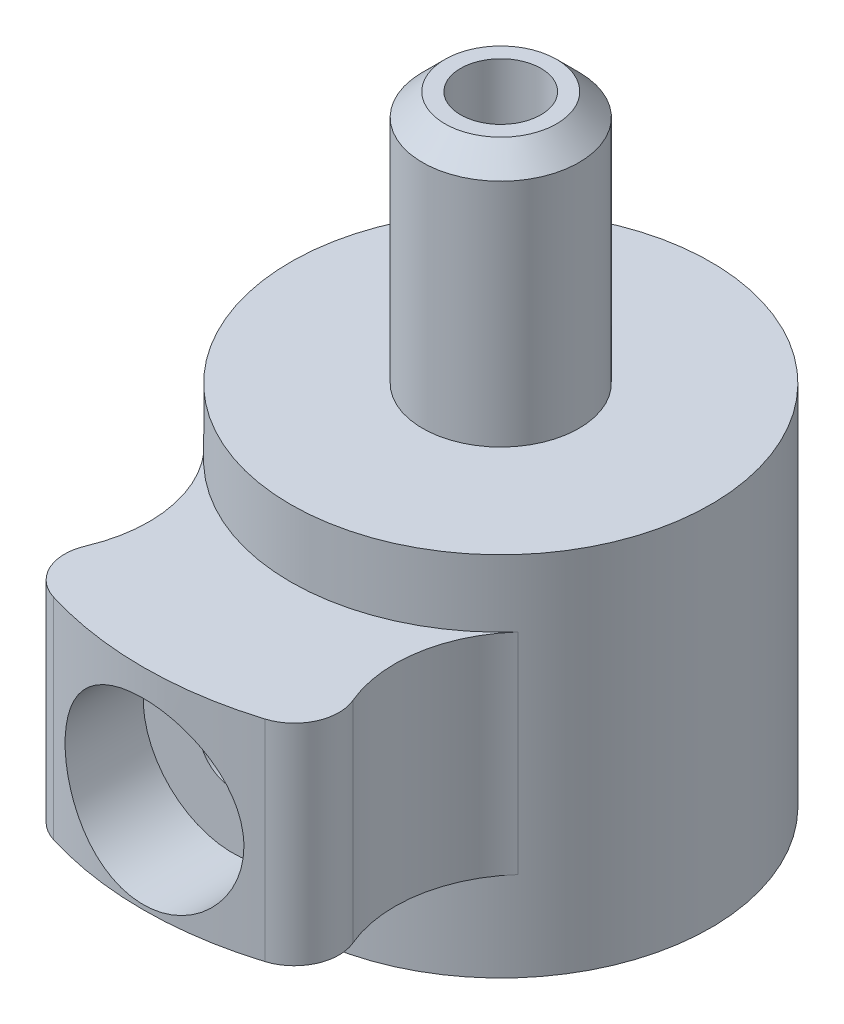
SolidWorks part; units mm, degrees
material "1060 Сплав"
ref_plane "Front Plane" through (0, 0, 0) normal (0, 0, 1) x (1, 0, 0)
ref_plane "Top Plane" through (0, 0, 0) normal (0, 1, 0) x (1, 0, 0)
ref_plane "Right Plane" through (0, 0, 0) normal (1, 0, 0) x (0, 0, -1)
sketch "Эскиз1" plane through (0, 0, 0) normal (1, 0, 0) x (0, 0, -1)
  line L0 (0, 0) -> (0, 10.689) construction
  line L1 (-3.4, 0) -> (-3.4, 6.5)
  line L2 (-3.4, 6.5) -> (-0.9, 6.5)
  line L3 (-0.9, 6.5) -> (-0.9, 13.85)
  line L4 (-0.9, 13.85) -> (-1.75, 13.85)
  line L5 (-1.75, 13.85) -> (-1.75, 8.2)
  line L6 (-1.75, 8.2) -> (-8, 8.2)
  line L7 (-8, 8.2) -> (-8, 0)
  line L8 (-8, 0) -> (-3.4, 0)
  line L9 (0, 0) -> (-3.4, 0) construction
  dimension "D1" = 6.8
  dimension "D2" = 1.8
  dimension "D3" = 3.5
  dimension "D4" = 16
  dimension "D5" = 8.2
  dimension "D6" = 13.85
  dimension "D7" = 6.5
revolve "Повернуть1" add sketch "Эскиз1" angle 360 about L0
sketch "Эскиз2" plane through (0, 8.2, 0) normal (0, 1, 0) x (1, 0, 0)
  line L0 (-5.75, -5.1213) -> (0, 0) construction
  line L1 (0, 0) -> (5.75, -5.1213) construction
  line L2 (-5.75, -5.1213) -> (5.75, -5.1213) construction
  line L3 (0, 0) -> (0, -5.1213) construction
  arc A0 (-5.75, -5.1213) -> (5.75, -5.1213) centre (0, 0) cw construction
  arc A1 (7.9903, -7.1166) -> (-7.9903, -7.1166) centre (0, 0) ccw
  arc A2 (3.5097, -3.126) -> (-3.5097, -3.126) centre (0, 0) ccw
  arc A3 (3.5097, -3.126) -> (7.9903, -7.1166) centre (5.75, -5.1213) ccw
  arc A4 (-7.9903, -7.1166) -> (-3.5097, -3.126) centre (-5.75, -5.1213) ccw
  point P4 (0, 7.7)
  dimension "D1" = 6
  dimension "D2" = 4.7
  dimension "D3" = 11.5
extrude "Вырез-Вытянуть1" cut sketch "Эскиз2" against normal through all
fillet "Скругление1" radius 1 2 edges at (3.5553, 4.1, 7.1666) (-3.5553, 4.1, 7.1666)
ref_plane "Плоскость1" through (0, 8.2, 8) normal (0, 0, 1) x (1, 0, 0)
sketch "Эскиз3" plane through (0, 8.2, 8) normal (0, 0, 1) x (1, 0, 0)
  line L0 (-2.3648, -4.1) -> (0, -4.1) construction
  line L1 (-2.3648, 0) -> (-2.3648, -8.2) construction
  line L2 (0, -4.1) -> (0, 0) construction
  line L3 (2.3648, 0) -> (-2.3648, 0) construction
  circle A0 centre (0, -4.1) radius 0.75
  dimension "D1" = 1.5
extrude "Вырез-Вытянуть2" cut sketch "Эскиз3" against normal up to next
sketch "Эскиз4" plane through (0, 8.2, 8) normal (0, 0, 1) x (1, 0, 0)
  circle A0 centre (0, -4.1) radius 2
  dimension "D1" = 4
extrude "Вырез-Вытянуть3" cut sketch "Эскиз4" against normal blind 2
sketch "Эскиз5" plane through (0, 8.2, 0) normal (0, 1, 0) x (1, 0, 0)
  circle A0 centre (0, 0) radius 4.7
extrude "Вырез-Вытянуть4" cut sketch "Эскиз5" against normal blind 1.5 flip side to cut
extrude "Вырез-Вытянуть5" cut sketch "Эскиз5<2>" along normal blind 2 from surface flip side to cut starting at face at (0, 0, -3.4)
sketch "Эскиз5<2>" plane through (0, 8.2, 0) normal (0, 1, 0) x (1, 0, 0) same geometry as "Эскиз5"
chamfer "Фаска1" distance 0.5 angle 45 1 edges at (0, 13.85, -1.75)
